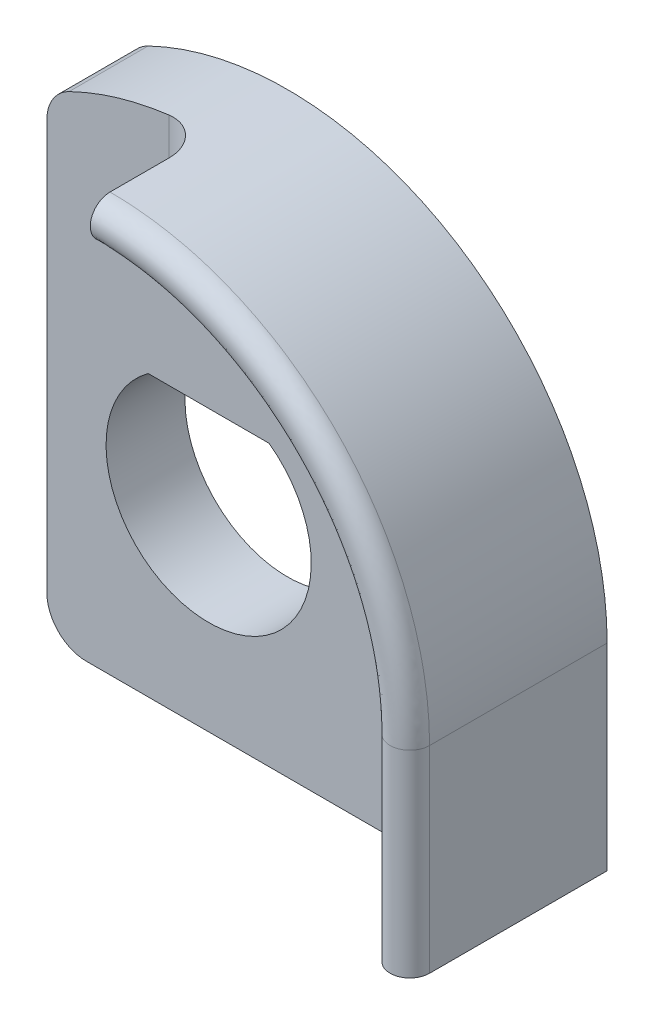
SolidWorks part; units mm, degrees
material "ABS"
ref_plane "Alzado" through (0, 0, 0) normal (0, 0, 1) x (1, 0, 0)
ref_plane "Planta" through (0, 0, 0) normal (0, 1, 0) x (1, 0, 0)
ref_plane "Vista lateral" through (0, 0, 0) normal (1, 0, 0) x (0, 0, -1)
sketch "Croquis1" plane through (0, 0, 0) normal (0, 0, 1) x (1, 0, 0)
  line L0 (0, 0) -> (0, -5) construction
  line L1 (8.1, 0) -> (8.1, -5)
  line L2 (-8.1, 0) -> (-8.1, -5)
  line L3 (-8.1, -5) -> (8.1, -5)
  arc A0 (8.1, 0) -> (-8.1, 0) centre (0, 0) ccw
  point P3 (0, -2.5)
  dimension "D1" = 8.1
  dimension "D2" = 5
extrude "Saliente-Extruir1" add sketch "Croquis1" along normal blind 2
sketch "Croquis4" plane through (0, 0, 2) normal (0, 0, 1) x (1, 0, 0)
  line L0 (-1.5, 2) -> (1.5, 2) construction
  line L1 (-1.533, 2.1) -> (1.533, 2.1)
  line L2 (0, 0) -> (0, -2.6) construction
  arc A0 (-1.5, 2) -> (1.5, 2) centre (0, 0) ccw construction
  arc A1 (-1.533, 2.1) -> (1.533, 2.1) centre (0, 0) ccw
  dimension "D1" = 5
  dimension "D3" = 0.1
  dimension "D2" = 3
  dimension "D4" = 0.1
extrude "Cortar-Extruir1" cut sketch "Croquis4" against normal up to next
sketch "Croquis5" plane through (0, 0, 2) normal (0, 0, 1) x (1, 0, 0)
  line L0 (-4.1, -5) -> (-4.1, 6.9857)
  line L1 (-8.1, -5) -> (8.1, -5) construction
  line L4 (-4.1, -5) -> (-8.1, -5)
  line L5 (-8.1, -5) -> (-8.1, 0)
  arc A0 (8.1, 0) -> (-8.1, 0) centre (0, 0) ccw construction
  arc A3 (-8.1, 0) -> (-4.1, 6.9857) centre (0, 0) cw
  dimension "D1" = 4.1
extrude "Cortar-Extruir2" cut sketch "Croquis5" against normal up to next
sketch "Croquis7" plane through (0, 0, 2) normal (0, 0, 1) x (1, 0, 0)
  line L0 (8.1, 0) -> (8.1, -5)
  line L1 (8.1, -5) -> (7.1, -5)
  line L2 (-4.1, -5) -> (8.1, -5) construction
  line L3 (7.1, -5) -> (7.1, 0)
  line L4 (0, 7.1) -> (0, 8.1)
  arc A0 (8.1, 0) -> (0, 8.1) centre (0, 0) ccw
  arc A1 (8.1, 0) -> (-4.1, 6.9857) centre (0, 0) ccw construction
  arc A2 (7.1, 0) -> (0, 7.1) centre (0, 0) ccw
  dimension "D1" = 1
extrude "Saliente-Extruir3" add sketch "Croquis7" along normal blind 3
fillet "Redondeo3" 4 edges at (5.0205, 5.0205, 5) (7.1, -2.5, 5) (5.7276, 5.7276, 5) (8.1, -2.5, 5) type full round first side face at (7.1, -2.5, 3.5) first side face at (4.2852, 4.2852, 3.5) second side face at (8.1, -2.5, 2.5) second side face at (1.938, 5.9432, 2.3333) middle face at (5.5913, 1.3913, 5)
fillet "Redondeo4" radius 1 3 edges at (-4.1, -5, 1) (-4.1, 6.9857, 1) (0, 7.6, 2)
